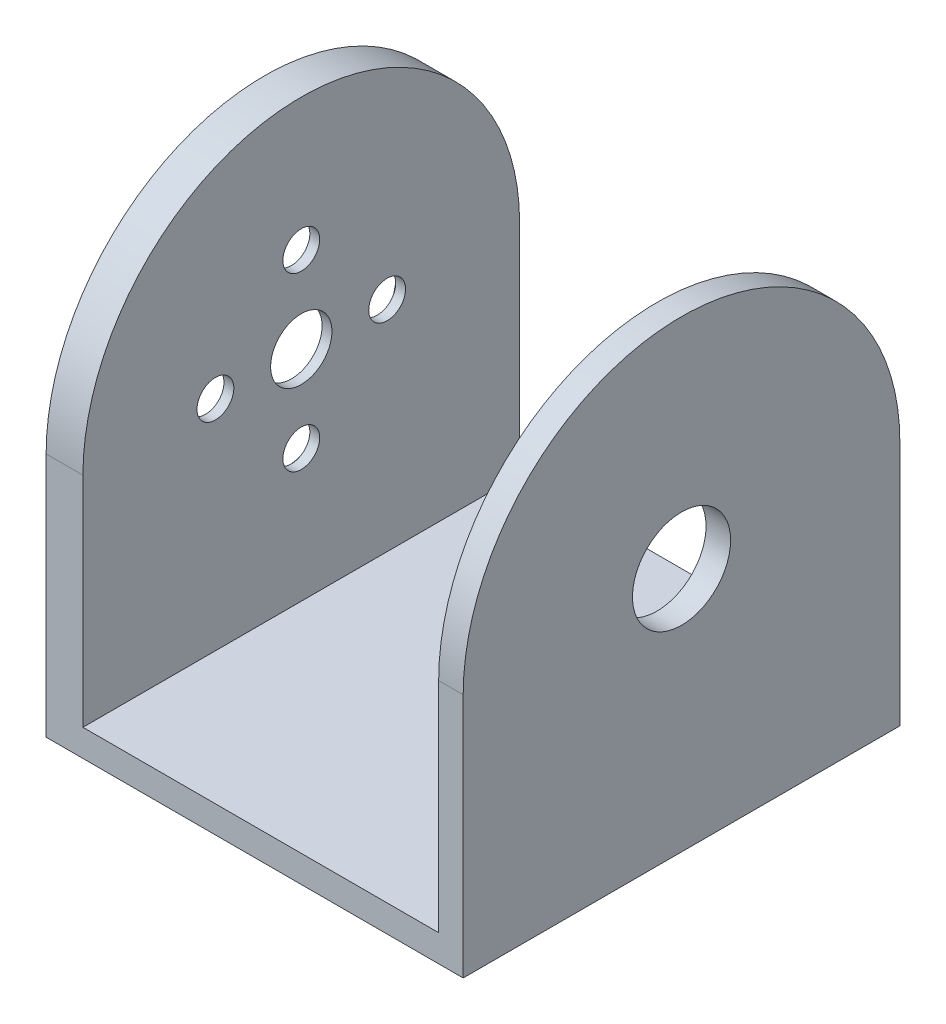
SolidWorks part; units mm, degrees
ref_plane "Front Plane" through (0, 0, 0) normal (0, 0, 1) x (1, 0, 0)
ref_plane "Top Plane" through (0, 0, 0) normal (0, 1, 0) x (1, 0, 0)
ref_plane "Right Plane" through (0, 0, 0) normal (1, 0, 0) x (0, 0, -1)
sketch "Sketch1" plane through (0, 0, 0) normal (0, 1, 0) x (1, 0, 0)
  line L1 (-17, -17.8) -> (17, -17.8)
  line L2 (-17, -17.8) -> (-17, 17.8)
  line L3 (-17, 17.8) -> (17, 17.8)
  line L4 (17, -17.8) -> (17, 17.8)
  line L5 (-17, -17.8) -> (17, 17.8) construction
  line L6 (-17, 17.8) -> (17, -17.8) construction
  point P0 (0, 0)
  dimension "D1" = 35.6
  dimension "D2" = 34
extrude "Boss-Extrude1" add sketch "Sketch1" along normal blind 2.2
sketch "Sketch3" plane through (-17, 0, 0) normal (-1, 0, 0) x (0, 0, 1)
  line L0 (0, 0) -> (0, 37.8) construction
  line L1 (-17.8, 2.2) -> (-17.8, 20)
  line L2 (17.8, 2.2) -> (17.8, 20)
  line L3 (-17.8, 2.2) -> (18.167, 2.2)
  arc A0 (-17.8, 20) -> (17.8, 20) centre (0, 20) cw
  line M3 (17.8, 2.2) -> (-17.8, 2.2)
  dimension "D1" = 17.8
extrude "Boss-Extrude2" add sketch "Sketch3" against normal blind 3 contours L0 L2 A0 M3 | L3 L0 A0 L1 region at (-17, 18.3384, -8.3081) region at (-17, 18.3384, 8.3081)
extrude "Boss-Extrude3" add sketch "Sketch3<4>" along normal blind 2 from surface contours L3 L0 A0 L1 | L0 L2 A0 M3 region at (-17, 18.3384, -8.3081) region at (-17, 18.3384, 8.3081) starting at face at (17, 1.1, 0)
sketch "Sketch3<4>" plane through (-17, 0, 0) normal (-1, 0, 0) x (0, 0, 1) same geometry as "Sketch3"
sketch "Sketch4" plane through (-17, 0, 0) normal (-1, 0, 0) x (0, 0, 1)
  line L0 (0, 37.8) -> (0, 0) construction
  line L1 (-17.8, 0) -> (17.8, 0) construction
  line L2 (-10.925, 20) -> (10.925, 20) construction
  circle A0 centre (0, 20) radius 10.925
  arc A1 (17.8, 20) -> (-17.8, 20) centre (0, 20) ccw construction
  circle A2 centre (0, 27) radius 1.5
  circle A3 centre (0, 13) radius 1.5
  circle A4 centre (-7, 20) radius 1.5
  circle A5 centre (7, 20) radius 1.5
  circle A6 centre (0, 20) radius 2.5
  dimension "D1" = 21.85
  dimension "D2" = 3
  dimension "D3" = 3
  dimension "D4" = 3
  dimension "D5" = 3
  dimension "D6" = 5
  dimension "D7" = 7
  dimension "D8" = 7
  dimension "D9" = 7
  dimension "D10" = 7
extrude "Cut-Extrude1" cut sketch "Sketch4" against normal blind 12 contours A6 | A5 | A2 | A4 | A3 region at (-17, 27, 0) region at (-17, 13, 0) region at (-17, 20, -7) region at (-17, 20, 7) region at (-17, 20, 0)
extrude "Cut-Extrude2" cut sketch "Sketch4<3>" against normal blind 2.2
sketch "Sketch4<3>" plane through (-17, 0, 0) normal (-1, 0, 0) x (0, 0, 1) same geometry as "Sketch4"
sketch "Sketch5" plane through (17, 0, 0) normal (1, 0, 0) x (0, 0, -1)
  line L0 (0, 37.8) -> (0, 0) construction
  arc A0 (17.8, 20) -> (-17.8, 20) centre (0, 20) ccw construction
  circle A1 centre (0, 20) radius 4
  dimension "D1" = 8
extrude "Cut-Extrude3" cut sketch "Sketch5" against normal blind 12.2
